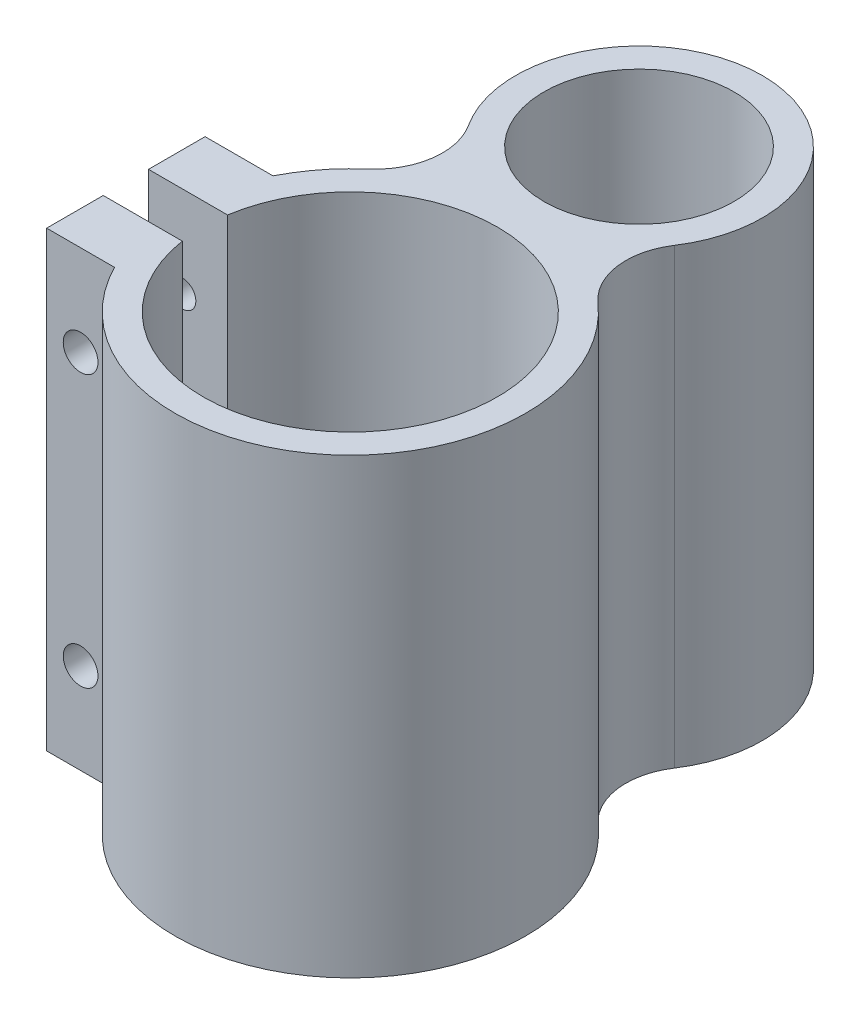
SolidWorks part; units mm, degrees
ref_plane "Front" through (0, 0, 0) normal (0, 0, 1) x (1, 0, 0)
ref_plane "Top" through (0, 0, 0) normal (0, 1, 0) x (1, 0, 0)
ref_plane "Right" through (0, 0, 0) normal (1, 0, 0) x (0, 0, -1)
ref_axis "Center Axis" through (0, 0, -88.99) along (0, 0, 1)
sketch "Sketch1" plane through (0, 0, 0) normal (0, 1, 0) x (1, 0, 0)
  line L1 (-3.6629, -20.8383) -> (-31.0082, -20.8383)
  line L2 (-3.6629, -20.8383) -> (-3.6629, -15.7583)
  line L3 (-3.6629, -15.7583) -> (-31.0082, -15.7583)
  line L4 (-31.0082, -20.8383) -> (-31.0082, -15.7583)
  line L5 (-3.6629, -20.8383) -> (-31.0082, -15.7583) construction
  line L6 (-3.6629, -15.7583) -> (-31.0082, -20.8383) construction
  line L7 (-17.3356, -15.7583) -> (-24.9556, -15.7583)
  line L8 (-17.3356, -15.7583) -> (-17.3356, -9.4083)
  line L9 (-17.3356, -9.4083) -> (-24.9556, -9.4083)
  line L10 (-24.9556, -15.7583) -> (-24.9556, -9.4083)
  line L11 (-17.3356, -20.8383) -> (-24.9556, -20.8383)
  line L12 (-17.3356, -20.8383) -> (-17.3356, -27.1883)
  line L13 (-17.3356, -27.1883) -> (-24.9556, -27.1883)
  line L14 (-24.9556, -20.8383) -> (-24.9556, -27.1883)
  circle A0 centre (0.3624, 13.9579) radius 10.668
  circle A1 centre (0.2277, -18.2983) radius 16.51
  circle A2 centre (0.3624, 13.9579) radius 13.843
  circle A3 centre (0.2277, -18.2983) radius 19.685
  point P4 (0.3624, 3.2899)
  point P6 (-18.095, -18.2983)
  point P9 (0.2277, -1.7883)
  point P11 (-17.3356, -18.2983)
  point P24 (-18.0497, -10.1405)
  dimension "D1" = 21.336
  dimension "D2" = 33.02
  dimension "D3" = 5.08
  dimension "D5" = 5.08
  dimension "D6" = 6.35
  dimension "D7" = 7.62
  dimension "D4" = 3.175
extrude "Boss-Extrude1" add sketch "Sketch1" along normal blind 50.8 contours A2 A3 A1 | A3 A2 A0 | A2 A3 | L8 L7 L10 L9 | L12 L11 L14 L13 region at (-16.7107, 0, 21.3767) region at (0.3073, 0, -0.7731) region at (-7.433, 0, -24.9265)
fillet "Fillet1" radius 7.62 2 edges at (-4.1895, 25.4, -0.8847) (4.8049, 25.4, -0.8471)
sketch "Sketch2" plane through (0, 0, 20.8383) normal (0, 0, -1) x (-1, 0, 0)
  line L0 (17.3356, 50.8) -> (24.9556, 50.8) construction
  line L1 (24.9556, 25.4) -> (17.3356, 25.4) construction
  line L2 (24.9556, 50.8) -> (24.9556, 0) construction
  line L3 (17.3356, 50.8) -> (17.3356, 0) construction
  circle A0 centre (21.1456, 40.64) radius 1.95
  circle A1 centre (21.1456, 10.16) radius 1.95
  point P3 (21.1456, 50.8)
  dimension "D1" = 3.9
  dimension "D2" = 15.24
extrude "Cut-Extrude1" cut sketch "Sketch2" against normal through all
sketch "Sketch3" plane through (0, 0, 9.4083) normal (0, 0, -1) x (-1, 0, 0)
  circle A0 centre (21.1456, 40.64) radius 1.5
  circle A1 centre (21.1456, 10.16) radius 1.95
  circle A2 centre (21.1456, 10.16) radius 1.95
  circle A3 centre (21.1456, 40.64) radius 1.95
  circle A4 centre (21.1456, 40.64) radius 1.95
  circle A5 centre (21.1456, 10.16) radius 1.5
  dimension "D3" = 3
  dimension "D1" = 0
  dimension "D2" = 0
extrude "Cut-Extrude3" cut sketch "Sketch3" against normal up to next contours A5 | A0 region at (-21.1456, 10.16, 9.4083)
